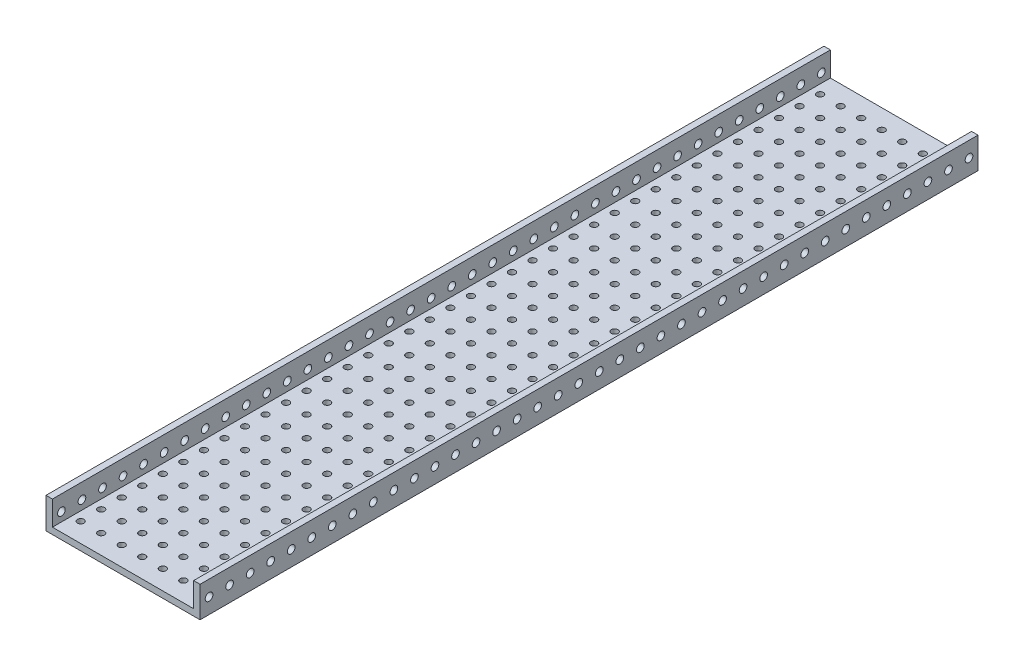
SolidWorks part; units mm, degrees
material "6061-T6 (SS)"
ref_plane "Front Plane" through (0, 0, 0) normal (0, 0, 1) x (1, 0, 0)
ref_plane "Top Plane" through (0, 0, 0) normal (0, 1, 0) x (1, 0, 0)
ref_plane "Right Plane" through (0, 0, 0) normal (1, 0, 0) x (0, 0, -1)
sketch "Sketch1" plane through (0, 0, 0) normal (0, 0, 1) x (1, 0, 0)
  line L0 (0, 0) -> (38.1, 0)
  line L1 (38.1, 0) -> (38.1, 15.24)
  line L2 (38.1, 15.24) -> (34.925, 15.24)
  line L3 (34.925, 15.24) -> (34.925, 3.175)
  line L4 (34.925, 3.175) -> (-34.925, 3.175)
  line L5 (-34.925, 3.175) -> (-34.925, 15.24)
  line L6 (-34.925, 15.24) -> (-38.1, 15.24)
  line L7 (-38.1, 15.24) -> (-38.1, 0)
  line L8 (-38.1, 0) -> (0, 0)
  dimension "D1" = 15.24
  dimension "D2" = 3.175
  dimension "D3" = 3.175
  dimension "D4" = 76.2
extrude "Extrude1" add sketch "Sketch1" along normal mid plane 384.81
sketch "Sketch2" plane through (0, 0, 0) normal (0, -1, 0) x (1, 0, 0)
  line L0 (-38.1, 192.405) -> (-30.48, 192.405) construction
  line L1 (-38.1, 192.405) -> (38.1, 192.405) construction
  line L2 (-30.48, 192.405) -> (-30.48, 186.055) construction
  dimension "D1" = 7.62
  dimension "D2" = 6.35
sketch "Sketch4" plane through (38.1, 0, 0) normal (1, 0, 0) x (0, 0, -1)
  line L0 (-192.405, 15.24) -> (-192.405, 7.62) construction
  line L1 (-192.405, 0) -> (-192.405, 15.24) construction
  line L2 (-192.405, 7.62) -> (-187.96, 7.62) construction
  line L3 (-187.96, 7.62) -> (-177.8, 7.62) construction
  dimension "D1" = 7.62
  dimension "D2" = 4.445
  dimension "D3" = 10.16
hole_wizard "#6 Clearance Hole1" positions "3DSketch1" profile "Sketch5" hole size "#6" standard "Ansi Inch" end condition through all
sketch3d "3DSketch1"
  point P0 (38.1, 7.62, 187.96)
sketch "Sketch5" plane through (38.1, 7.62, 187.96) normal (0, 1, 0) x (0, 0, -1)
  line L0 (0, 0) -> (0, 76.2)
  line L1 (0, 76.2) -> (1.8986, 76.2)
  line L2 (1.8986, 76.2) -> (1.8986, 0)
  line L5 (1.8986, 0) -> (0, 0)
  line L11 (0, -6.35) -> (0, 107.95) construction
  dimension "Thru Hole Dia." = 3.7973
  dimension "Thru Hole Depth" = 76.2
pattern_linear "LPattern1" count 38 spacing 10.16 along (0, 0, -1) of "#6 Clearance Hole1"
sketch "Sketch6" plane through (0, 0, 0) normal (0, -1, 0) x (1, 0, 0)
  line L0 (38.1, 182.88) -> (-38.1, 182.88) construction
  line L1 (0, 182.88) -> (5.08, 182.88) construction
  line L2 (0, 182.88) -> (-5.08, 182.88) construction
  line L5 (-38.1, 192.405) -> (38.1, 192.405) construction
  point P4 (0, 182.88)
  dimension "D1" = 5.08
  dimension "D2" = 5.08
  dimension "D3" = 9.525
hole_wizard "#4 Clearance Hole1" positions "3DSketch2" profile "Sketch7" hole size "#4" standard "Ansi Inch" end condition through all
sketch3d "3DSketch2"
  point P7 (0, 0, 182.88)
sketch "Sketch7" plane through (0, 0, 182.88) normal (1, 0, 0) x (0, 0, -1)
  line L0 (0, 0) -> (0, 15.24)
  line L1 (0, 15.24) -> (1.6319, 15.24)
  line L2 (1.6319, 15.24) -> (1.6319, 0)
  line L5 (1.6319, 0) -> (0, 0)
  line L11 (0, -6.35) -> (0, 107.95) construction
  dimension "Thru Hole Dia." = 3.2639
  dimension "Thru Hole Depth" = 15.24
pattern_linear "LPattern2" count 4 spacing 10.16 along (1, 0, 0) count 4 spacing 10.16 along (-1, 0, 0) of "#4 Clearance Hole1"
pattern_linear "LPattern3" count 37 spacing 10.16 along (0, 0, -1) of "LPattern2", "#4 Clearance Hole1"
sketch "Sketch8" plane through (0, 0, -192.405) normal (0, 0, -1) x (-1, 0, 0)
  line L0 (-38.1, 15.24) -> (-38.1, 40.64) construction
  dimension "D1" = 25.4
